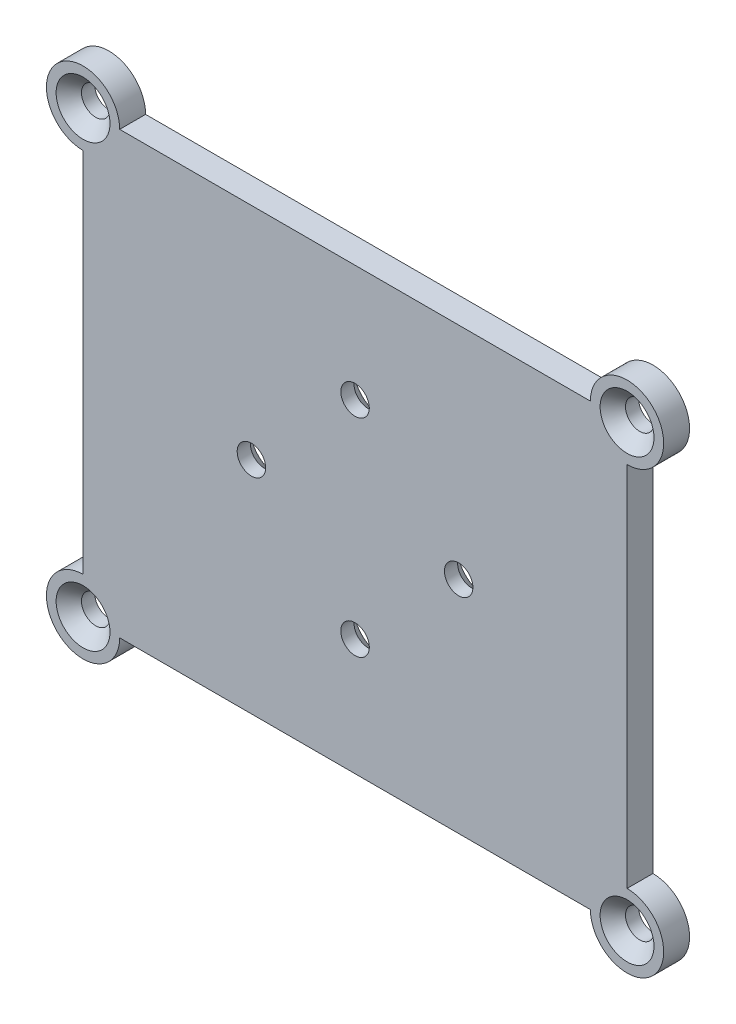
SolidWorks part; units mm, degrees
ref_plane "Front Plane" through (0, 0, 0) normal (1, 0, 0) x (0, 1, 0)
ref_plane "Top Plane" through (0, 0, 0) normal (0, 0, 1) x (0, 1, 0)
ref_plane "Right Plane" through (0, 0, 0) normal (0, 1, 0) x (-1, 0, 0)
sketch "Sketch1" plane through (0, 0, 0) normal (0, 0, 1) x (0, 1, 0)
  line L0 (0, 0) -> (0, 20) construction
  line L1 (-37.5, -47.5) -> (37.5, -47.5)
  line L2 (-37.5, -47.5) -> (-37.5, 47.5)
  line L3 (-37.5, 47.5) -> (37.5, 47.5)
  line L4 (37.5, -47.5) -> (37.5, 47.5)
  line L5 (-37.5, -47.5) -> (37.5, 47.5) construction
  line L6 (-37.5, 47.5) -> (37.5, -47.5) construction
  circle A0 centre (0, 20) radius 1
  circle A1 centre (20, 0) radius 1
  circle A2 centre (0, -20) radius 1
  circle A3 centre (-20, 0) radius 1
  point P0 (0, 0)
  point P9 (12.0553, -29.9993)
  point P10 (0, 0)
  point P18 (0, 0)
  dimension "D3" = 2
  dimension "D4" = 20
  dimension "D1" = 95
  dimension "D2" = 75
  dimension "D5" = 4
extrude "Boss-Extrude1" add sketch "Sketch1" along normal blind 5
hole_wizard "CSK for M5 Flat Head Machine Screw1" positions "3DSketch1" profile "Sketch2" countersink size "M5" standard "ANSI Metric" end condition through all
sketch3d "3DSketch1"
  line L0 (0, 20, 5) -> (0, 20, 0) construction
  line L1 (-20, 0, 5) -> (-20, 0, 0) construction
  line L2 (0, -20, 5) -> (0, -20, 0) construction
  line L3 (20, 0, 5) -> (20, 0, 0) construction
  point P0 (0, 20, 0)
  point P4 (-20, 0, 0)
  point P8 (0, -20, 0)
  point P12 (20, 0, 0)
sketch "Sketch2" plane through (0, 20, 0) normal (1, 0, 0) x (0, 1, 0)
  line L0 (0, 0) -> (0, 5)
  line L1 (0, 5) -> (2.75, 5)
  line L2 (2.75, 5) -> (2.75, 2.45)
  line L3 (2.75, 2.45) -> (5.2, 0)
  line L5 (5.2, 0) -> (0, 0)
  line L6 (-2.75, 2.45) -> (-5.2, 0) construction
  line L11 (0, -6.35) -> (0, 107.95) construction
  dimension "Thru Hole Dia." = 5.5
  dimension "Thru Hole Depth" = 5
  dimension "Near C'Sink Dia." = 10.4
  dimension "Near C'Sink Angle" = 90
sketch "Sketch3" plane through (0, 0, 5) normal (0, 0, 1) x (1, 0, 0)
  line L0 (47.5, 37.5) -> (-47.5, 37.5) construction
  line L1 (-52.5, -42.5) -> (52.5, -42.5)
  line L2 (-52.5, -42.5) -> (-52.5, 42.5)
  line L3 (-52.5, 42.5) -> (52.5, 42.5)
  line L4 (52.5, -42.5) -> (52.5, 42.5)
  line L5 (-52.5, -42.5) -> (52.5, 42.5) construction
  line L6 (-52.5, 42.5) -> (52.5, -42.5) construction
  line L7 (-47.5, 37.5) -> (-47.5, -37.5) construction
  line L9 (-47.5, -37.5) -> (47.5, -37.5)
  line L10 (-47.5, -37.5) -> (-47.5, 37.5)
  line L11 (-47.5, 37.5) -> (47.5, 37.5)
  line L12 (47.5, -37.5) -> (47.5, 37.5)
  line L13 (-47.5, -37.5) -> (47.5, 37.5) construction
  line L14 (-47.5, 37.5) -> (47.5, -37.5) construction
  circle A0 centre (-52.5, 42.5) radius 7.0711
  circle A1 centre (52.5, 42.5) radius 7.0711
  circle A2 centre (52.5, -42.5) radius 7.0711
  circle A3 centre (-52.5, -42.5) radius 7.0711
  point P0 (0, 0)
  point P18 (0, 0)
  line M7 (47.5, 37.5) -> (-47.5, 37.5)
  line M8 (-47.5, 37.5) -> (-47.5, -37.5)
  line M9 (-47.5, -37.5) -> (47.5, -37.5)
  line M10 (47.5, -37.5) -> (47.5, 37.5)
  dimension "D1" = 5
  dimension "D2" = 5
extrude "Boss-Extrude2" add sketch "Sketch3" against normal blind 5 contours L3 A0 L2 | L2 A0 L3 | A1 L3 A0 M7 | L4 A1 L3 | L3 A1 L4 | A2 L4 A1 M10 | L4 A2 L1 | L1 A2 L4 | A3 L1 A2 M9 | L1 A3 L2 | L2 A3 L1 | A3 A0 L2 M8 region at (-49.4989, -39.4989, 5) region at (-53.5004, -43.5004, 5) region at (0, -39.982, 5) region at (-49.977, 0, 5) region at (49.4989, -39.4989, 5) region at (53.5004, -43.5004, 5) region at (-53.5004, 43.5004, 5) region at (-49.4989, 39.4989, 5) region at (49.977, 0, 5) region at (0, 39.982, 5) region at (49.4989, 39.4989, 5) region at (53.5004, 43.5004, 5)
sketch "Sketch4" plane through (0, 0, 5) normal (0, 0, 1) x (1, 0, 0)
  point P0 (-52.5, 42.5)
  point P1 (52.5, 42.5)
  point P3 (52.5, -42.5)
  point P5 (-52.5, -42.5)
hole_wizard "CSK for M5 Flat Head Machine Screw2" positions "Sketch4" profile "Sketch5" countersink size "M5" standard "ANSI Metric" end condition through all
sketch "Sketch5" plane through (-52.5, 42.5, 5) normal (1, 0, 0) x (0, -1, 0)
  line L0 (0, 0) -> (0, 5)
  line L1 (0, 5) -> (2.75, 5)
  line L2 (2.75, 5) -> (2.75, 2.45)
  line L3 (2.75, 2.45) -> (5.2, 0)
  line L5 (5.2, 0) -> (0, 0)
  line L6 (-2.75, 2.45) -> (-5.2, 0) construction
  line L11 (0, -6.35) -> (0, 107.95) construction
  dimension "Thru Hole Dia." = 5.5
  dimension "Thru Hole Depth" = 5
  dimension "Near C'Sink Dia." = 10.4
  dimension "Near C'Sink Angle" = 90
